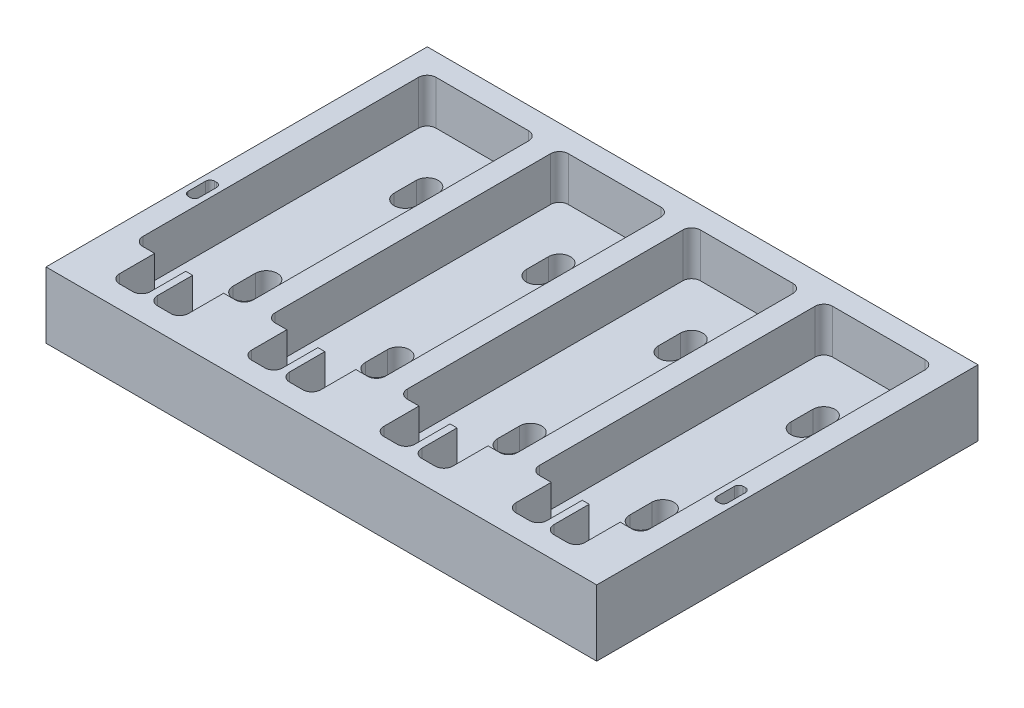
SolidWorks part; units mm, degrees
ref_plane "Front Plane" through (0, 0, 0) normal (0, 0, 1) x (1, 0, 0)
ref_plane "Top Plane" through (0, 0, 0) normal (0, 1, 0) x (1, 0, 0)
ref_plane "Right Plane" through (0, 0, 0) normal (1, 0, 0) x (0, 0, -1)
sketch "Sketch3" plane through (0, 0, 0) normal (0, 1, 0) x (1, 0, 0)
  line L0 (85.09, 19.05) -> (111.76, 19.05)
  line L1 (0, 0) -> (158.75, 0)
  line L2 (0, 0) -> (0, 109.9058)
  line L3 (0, 109.9058) -> (158.75, 109.9058)
  line L4 (158.75, 0) -> (158.75, 109.9058)
  line L6 (6.35, 95.9358) -> (6.35, 24.765)
  line L7 (21.4376, 19.05) -> (23.0124, 19.05)
  line L8 (38.1, 101.0158) -> (38.1, 29.845)
  line L9 (44.45, 101.0158) -> (44.45, 29.845)
  line L10 (59.5884, 19.05) -> (61.0616, 19.05)
  line L11 (76.2, 101.0158) -> (76.2, 29.845)
  line L13 (82.55, 101.0158) -> (82.55, 29.8069)
  line L14 (90.0544, 19.05) -> (106.7956, 19.05)
  line L15 (114.3, 101.0158) -> (114.3, 29.4066)
  line L18 (123.19, 19.05) -> (149.86, 19.05)
  line L20 (22.225, 103.5558) -> (22.225, 19.05) construction
  line L21 (21.4376, 19.05) -> (36.8492, 19.05) construction
  line L22 (88.4842, 19.05) -> (88.4842, 8.89)
  line L23 (94.885, 6.35) -> (91.0242, 6.35)
  line L24 (97.425, 19.05) -> (97.425, 8.89)
  line L25 (60.325, 19.05) -> (60.325, 0) construction
  line L26 (98.425, 19.05) -> (98.425, 0) construction
  line L27 (136.525, 19.05) -> (136.525, 0) construction
  line L28 (50.3842, 19.05) -> (59.325, 19.05)
  line L29 (50.3842, 19.05) -> (50.3842, 8.89)
  line L30 (52.9242, 6.35) -> (56.785, 6.35)
  line L31 (59.325, 19.05) -> (59.325, 8.89)
  line L32 (68.8492, 19.05) -> (78.3492, 19.05)
  line L33 (22.225, 19.05) -> (22.225, 0) construction
  line L34 (23.225, 19.05) -> (23.225, 8.89)
  line L35 (29.6258, 6.35) -> (25.765, 6.35)
  line L36 (12.2842, 19.05) -> (21.225, 19.05)
  line L37 (12.2842, 19.05) -> (12.2842, 8.89)
  line L38 (14.8242, 6.35) -> (18.685, 6.35)
  line L39 (21.225, 19.05) -> (21.225, 8.89)
  line L40 (97.425, 19.05) -> (88.4842, 19.05)
  line L41 (70.2658, 19.05) -> (70.2658, 8.89)
  line L42 (67.7258, 6.35) -> (63.865, 6.35)
  line L43 (61.325, 19.05) -> (61.325, 8.89)
  line L44 (108.3492, 19.05) -> (98.8492, 19.05)
  line L45 (138.3492, 19.05) -> (128.8492, 19.05) construction
  line L46 (108.3658, 19.05) -> (108.3658, 8.89)
  line L47 (101.965, 6.35) -> (105.8258, 6.35)
  line L48 (99.425, 19.05) -> (99.425, 8.89)
  line L49 (138.3492, 19.05) -> (128.8492, 19.05)
  line L50 (126.5842, 19.05) -> (126.5842, 8.89)
  line L51 (132.985, 6.35) -> (129.1242, 6.35)
  line L52 (32.1658, 19.05) -> (32.1658, 8.89)
  line L53 (135.525, 19.05) -> (135.525, 8.89)
  line L54 (135.525, 19.05) -> (126.5842, 19.05)
  line L55 (60.325, 19.05) -> (60.325, 103.5558) construction
  line L57 (98.425, 103.5558) -> (98.425, 19.05) construction
  line L58 (136.525, 100.33) -> (136.525, 19.05) construction
  line L59 (146.4658, 19.05) -> (146.4658, 8.89)
  line L60 (140.065, 6.35) -> (143.9258, 6.35)
  line L61 (137.525, 19.05) -> (137.525, 8.89)
  line L63 (8.89, 103.5558) -> (35.56, 103.5558)
  line L64 (6.35, 101.0158) -> (6.35, 21.59)
  line L65 (8.89, 19.05) -> (35.56, 19.05)
  line L66 (38.1, 101.0158) -> (38.1, 21.59)
  line L67 (46.99, 103.5558) -> (73.66, 103.5558)
  line L68 (44.45, 101.0158) -> (44.45, 21.59)
  line L69 (46.99, 19.05) -> (73.66, 19.05)
  line L70 (76.2, 101.0158) -> (76.2, 21.59)
  line L71 (85.09, 103.5558) -> (111.76, 103.5558)
  line L72 (82.55, 101.0158) -> (82.55, 21.59)
  line L74 (123.19, 103.5558) -> (149.86, 103.5558)
  line L76 (114.3, 101.0158) -> (114.3, 21.59)
  line L77 (120.65, 101.0158) -> (120.65, 21.59)
  line L78 (123.19, 19.05) -> (149.86, 19.05)
  line L79 (152.4, 101.0158) -> (152.4, 21.59)
  arc A0 (152.4, 101.0158) -> (149.86, 103.5558) centre (149.86, 101.0158) ccw
  arc A1 (123.19, 19.05) -> (120.65, 21.59) centre (123.19, 21.59) cw
  arc A2 (85.09, 103.5558) -> (82.55, 101.0158) centre (85.09, 101.0158) ccw
  arc A3 (114.3, 101.0158) -> (111.76, 103.5558) centre (111.76, 101.0158) ccw
  arc A4 (123.19, 103.5558) -> (120.65, 101.0158) centre (123.19, 101.0158) ccw
  arc A5 (152.4, 21.59) -> (149.86, 19.05) centre (149.86, 21.59) cw
  arc A6 (38.1, 101.0158) -> (35.56, 103.5558) centre (35.56, 101.0158) ccw
  arc A7 (8.89, 103.5558) -> (6.35, 101.0158) centre (8.89, 101.0158) ccw
  arc A8 (8.89, 19.05) -> (6.35, 21.59) centre (8.89, 21.59) cw
  arc A9 (38.1, 21.59) -> (35.56, 19.05) centre (35.56, 21.59) cw
  arc A10 (44.45, 21.59) -> (46.99, 19.05) centre (46.99, 21.59) ccw
  arc A11 (73.66, 19.05) -> (76.2, 21.59) centre (73.66, 21.59) ccw
  arc A12 (46.99, 103.5558) -> (44.45, 101.0158) centre (46.99, 101.0158) ccw
  arc A13 (76.2, 101.0158) -> (73.66, 103.5558) centre (73.66, 101.0158) ccw
  arc A14 (114.3, 21.59) -> (111.76, 19.05) centre (111.76, 21.59) cw
  arc A15 (82.55, 21.59) -> (85.09, 19.05) centre (85.09, 21.59) ccw
  arc A16 (126.5842, 8.89) -> (129.1242, 6.35) centre (129.1242, 8.89) ccw
  arc A17 (132.985, 6.35) -> (135.525, 8.89) centre (132.985, 8.89) ccw
  arc A18 (140.065, 6.35) -> (137.525, 8.89) centre (140.065, 8.89) cw
  arc A19 (146.4658, 8.89) -> (143.9258, 6.35) centre (143.9258, 8.89) cw
  arc A20 (108.3658, 8.89) -> (105.8258, 6.35) centre (105.8258, 8.89) cw
  arc A21 (101.965, 6.35) -> (99.425, 8.89) centre (101.965, 8.89) cw
  arc A22 (94.885, 6.35) -> (97.425, 8.89) centre (94.885, 8.89) ccw
  arc A23 (88.4842, 8.89) -> (91.0242, 6.35) centre (91.0242, 8.89) ccw
  arc A24 (70.2658, 8.89) -> (67.7258, 6.35) centre (67.7258, 8.89) cw
  arc A25 (63.865, 6.35) -> (61.325, 8.89) centre (63.865, 8.89) cw
  arc A26 (56.785, 6.35) -> (59.325, 8.89) centre (56.785, 8.89) ccw
  arc A27 (50.3842, 8.89) -> (52.9242, 6.35) centre (52.9242, 8.89) ccw
  arc A28 (29.6258, 6.35) -> (32.1658, 8.89) centre (29.6258, 8.89) ccw
  arc A29 (23.225, 8.89) -> (25.765, 6.35) centre (25.765, 8.89) ccw
  arc A30 (18.685, 6.35) -> (21.225, 8.89) centre (18.685, 8.89) ccw
  arc A31 (12.2842, 8.89) -> (14.8242, 6.35) centre (14.8242, 8.89) ccw
  point P79 (82.55, 103.5558)
  point P82 (114.3, 103.5558)
  point P89 (38.1, 103.5558)
  point P92 (6.35, 103.5558)
  point P95 (6.35, 19.05)
  point P98 (38.1, 19.05)
  point P101 (44.45, 19.05)
  point P112 (76.2, 19.05)
  point P115 (44.45, 103.5558)
  point P119 (22.225, 103.5558)
  point P120 (60.325, 103.5558)
  point P130 (98.425, 103.5558)
  point P131 (136.525, 103.5558)
  point P133 (76.2, 103.5558)
  point P138 (82.55, 19.05)
  point P141 (126.5842, 6.35)
  point P144 (135.525, 6.35)
  point P147 (137.525, 6.35)
  point P150 (146.4658, 6.35)
  point P153 (108.3658, 6.35)
  point P156 (99.425, 6.35)
  point P159 (97.425, 6.35)
  point P162 (88.4842, 6.35)
  point P165 (70.2658, 6.35)
  point P168 (61.325, 6.35)
  point P171 (59.325, 6.35)
  point P174 (50.3842, 6.35)
  point P177 (32.1658, 6.35)
  point P180 (23.225, 6.35)
  point P183 (21.225, 6.35)
  point P186 (12.2842, 6.35)
  dimension "D22" = 2.54
  dimension "D25" = 103.5558
  dimension "D26" = 31.75
  dimension "D27" = 2.54
  dimension "D28" = 6.35
  dimension "D5" = 2.54
  dimension "D17" = 2.54
  dimension "D24" = 2.54
  dimension "D1" = 6.35
  dimension "D3" = 6.35
  dimension "D4" = 103.5558
  dimension "D6" = 6.35
  dimension "D7" = 1
  dimension "D8" = 8.9408
  dimension "D9" = 8.9408
  dimension "D10" = 8.9408
  dimension "D11" = 31.75
  dimension "D12" = 6.35
  dimension "D13" = 6.35
  dimension "D14" = 6.35
  dimension "D15" = 31.75
  dimension "D16" = 31.75
  dimension "D18" = 8.9408
  dimension "D19" = 1
  dimension "D20" = 1
  dimension "D21" = 1
  dimension "D23" = 12.7
extrude "Boss-Extrude4" add sketch "Sketch3" against normal blind 19.05 contours L39 L7 L37 L38 | L7 | L8 L6 L7 | L31 L10 L29 L30 | L11 L9 L10 | L15 L13 L14 | L24 L14 L22 L23 | L14 | L53 L18 L50 L51 | L18 | L10 | L1 L4 L3 L2 L10 L31 L30 L29 L9 L11 L7 L39 L38 L37 L6 L8 L14 L24 L23 L22 L13 L15 L18 L53 L51 L50 | L18 | L52 L7 L34 L35 | A25 L42 A24 L41 L32 L69 L43 | A21 L47 A20 L46 L0 L44 L48 | A19 L59 L18 L61 A18 L60 region at (98.425, 0, -61.3029) region at (92.9546, 0, -12.8445) region at (103.8954, 0, -12.8445) region at (79.375, 0, -49.7076) region at (22.225, 0, -61.3029) region at (16.7546, 0, -12.8445) region at (27.6954, 0, -12.8445) region at (60.325, 0, -61.3029) region at (54.8546, 0, -12.8445) region at (65.7954, 0, -12.8445) region at (136.525, 0, -61.3029) region at (131.0546, 0, -12.8445) region at (141.9954, 0, -12.8445)
extrude "Cut-Extrude7" cut sketch "Sketch3<12>" against normal blind 12.7 contours L8 L6 L7 | L11 L9 L10 L32 | L31 L10 L29 L30 | L32 L43 L42 L41 L10 | L15 L13 L14 L40 L44 | L24 L40 L14 L22 L23 | L18 L49 | L53 L18 L50 L51 | L18 L61 L60 L59 | L44 L48 L47 L46 L14 | L39 L7 L37 L38 | L52 L7 L34 L35 | L37 A31 L38 A30 L39 L36 region at (98.425, 0, -61.3029) region at (92.9546, 0, -12.8445) region at (103.8954, 0, -12.8445) region at (22.225, 0, -61.3029) region at (16.7546, 0, -12.8445) region at (27.6954, 0, -12.8445) region at (60.325, 0, -61.3029) region at (54.8546, 0, -12.8445) region at (65.7954, 0, -12.8445) region at (136.525, 0, -61.3029) region at (131.0546, 0, -12.8445) region at (141.9954, 0, -12.8445)
sketch "Sketch3<12>" plane through (0, 0, 0) normal (0, 1, 0) x (1, 0, 0) same geometry as "Sketch3"
sketch "Sketch5" plane through (0, -12.7, 0) normal (0, 1, 0) x (1, 0, 0)
  line L0 (22.225, 103.5558) -> (22.225, 0) construction
  line L2 (0, 0) -> (158.75, 0) construction
  line L3 (60.325, 103.5558) -> (60.325, 0) construction
  line L5 (98.425, 103.5558) -> (98.425, 0) construction
  line L7 (136.525, 103.5558) -> (136.525, 0) construction
  line L9 (22.225, 87.6808) -> (22.225, 81.3308) construction
  line L10 (25.4, 87.6808) -> (25.4, 81.3308)
  line L11 (19.05, 87.6808) -> (19.05, 81.3308)
  line L12 (22.225, 41.275) -> (22.225, 34.925) construction
  line L13 (25.4, 41.275) -> (25.4, 34.925)
  line L14 (19.05, 41.275) -> (19.05, 34.925)
  line L15 (60.325, 34.925) -> (60.325, 41.275) construction
  line L16 (57.15, 34.925) -> (57.15, 41.275)
  line L17 (63.5, 34.925) -> (63.5, 41.275)
  line L18 (60.325, 81.3308) -> (60.325, 87.6808) construction
  line L19 (57.15, 81.3308) -> (57.15, 87.6808)
  line L20 (63.5, 81.3308) -> (63.5, 87.6808)
  line L21 (98.425, 87.6808) -> (98.425, 81.3308) construction
  line L22 (101.6, 87.6808) -> (101.6, 81.3308)
  line L23 (95.25, 87.6808) -> (95.25, 81.3308)
  line L24 (98.425, 41.275) -> (98.425, 34.925) construction
  line L25 (101.6, 41.275) -> (101.6, 34.925)
  line L26 (95.25, 41.275) -> (95.25, 34.925)
  line L27 (136.525, 41.275) -> (136.525, 34.925) construction
  line L28 (139.7, 41.275) -> (139.7, 34.925)
  line L29 (133.35, 41.275) -> (133.35, 34.925)
  line L30 (136.525, 87.6808) -> (136.525, 81.3308) construction
  line L31 (139.7, 87.6808) -> (139.7, 81.3308)
  line L32 (133.35, 87.6808) -> (133.35, 81.3308)
  line L33 (21.225, 19.05) -> (23.225, 19.05) construction
  line L35 (59.325, 19.05) -> (61.325, 19.05) construction
  line L36 (97.425, 19.05) -> (99.425, 19.05) construction
  line L37 (135.525, 19.05) -> (137.525, 19.05) construction
  line L40 (8.89, 103.5558) -> (35.56, 103.5558) construction
  line L41 (46.99, 103.5558) -> (73.66, 103.5558) construction
  line L42 (85.09, 103.5558) -> (111.76, 103.5558) construction
  line L43 (123.19, 103.5558) -> (149.86, 103.5558) construction
  arc A0 (25.4, 87.6808) -> (19.05, 87.6808) centre (22.225, 87.6808) ccw
  arc A1 (19.05, 81.3308) -> (25.4, 81.3308) centre (22.225, 81.3308) ccw
  arc A2 (25.4, 41.275) -> (19.05, 41.275) centre (22.225, 41.275) ccw
  arc A3 (19.05, 34.925) -> (25.4, 34.925) centre (22.225, 34.925) ccw
  arc A4 (57.15, 34.925) -> (63.5, 34.925) centre (60.325, 34.925) ccw
  arc A5 (63.5, 41.275) -> (57.15, 41.275) centre (60.325, 41.275) ccw
  arc A6 (57.15, 81.3308) -> (63.5, 81.3308) centre (60.325, 81.3308) ccw
  arc A7 (63.5, 87.6808) -> (57.15, 87.6808) centre (60.325, 87.6808) ccw
  arc A8 (101.6, 87.6808) -> (95.25, 87.6808) centre (98.425, 87.6808) ccw
  arc A9 (95.25, 81.3308) -> (101.6, 81.3308) centre (98.425, 81.3308) ccw
  arc A10 (101.6, 41.275) -> (95.25, 41.275) centre (98.425, 41.275) ccw
  arc A11 (95.25, 34.925) -> (101.6, 34.925) centre (98.425, 34.925) ccw
  arc A12 (139.7, 41.275) -> (133.35, 41.275) centre (136.525, 41.275) ccw
  arc A13 (133.35, 34.925) -> (139.7, 34.925) centre (136.525, 34.925) ccw
  arc A14 (139.7, 87.6808) -> (133.35, 87.6808) centre (136.525, 87.6808) ccw
  arc A15 (133.35, 81.3308) -> (139.7, 81.3308) centre (136.525, 81.3308) ccw
  point P20 (22.225, 84.5058)
  point P25 (22.225, 38.1)
  point P32 (60.325, 38.1)
  point P39 (60.325, 84.5058)
  point P46 (98.425, 84.5058)
  point P53 (98.425, 38.1)
  point P60 (136.525, 38.1)
  point P67 (136.525, 84.5058)
  dimension "D1" = 6.35
  dimension "D2" = 6.35
  dimension "D3" = 6.35
  dimension "D4" = 6.35
  dimension "D5" = 6.35
  dimension "D6" = 6.35
  dimension "D7" = 19.05
  dimension "D8" = 19.05
  dimension "D9" = 19.05
  dimension "D10" = 6.35
  dimension "D11" = 6.35
  dimension "D12" = 19.05
  dimension "D13" = 6.35
  dimension "D14" = 6.35
  dimension "D15" = 19.05
  dimension "D16" = 6.35
  dimension "D17" = 6.35
  dimension "D18" = 19.05
  dimension "D19" = 6.35
  dimension "D20" = 6.35
  dimension "D21" = 19.05
  dimension "D22" = 6.35
  dimension "D23" = 6.35
  dimension "D24" = 19.05
extrude "Cut-Extrude8" cut sketch "Sketch5" against normal through all
sketch "Sketch7" plane through (0, 0, 0) normal (0, 1, 0) x (1, 0, 0)
  line L0 (0, 0) -> (0, 109.9058) construction
  line L1 (2.8575, 45.72) -> (3.4925, 45.72)
  line L2 (1.5875, 44.45) -> (1.5875, 39.37)
  line L3 (2.8575, 38.1) -> (3.4925, 38.1)
  line L4 (4.7625, 44.45) -> (4.7625, 39.37)
  line L5 (0, 0) -> (158.75, 0) construction
  line L6 (79.375, 109.9058) -> (79.375, 0) construction
  line L7 (0, 109.9058) -> (158.75, 109.9058) construction
  line L8 (153.9875, 44.45) -> (153.9875, 39.37)
  line L9 (155.8925, 38.1) -> (155.2575, 38.1)
  line L10 (157.1625, 44.45) -> (157.1625, 39.37)
  line L11 (155.8925, 45.72) -> (155.2575, 45.72)
  arc A0 (3.4925, 38.1) -> (4.7625, 39.37) centre (3.4925, 39.37) ccw
  arc A1 (1.5875, 39.37) -> (2.8575, 38.1) centre (2.8575, 39.37) ccw
  arc A2 (3.4925, 45.72) -> (4.7625, 44.45) centre (3.4925, 44.45) cw
  arc A3 (2.8575, 45.72) -> (1.5875, 44.45) centre (2.8575, 44.45) ccw
  arc A4 (153.9875, 39.37) -> (155.2575, 38.1) centre (155.2575, 39.37) ccw
  arc A5 (155.8925, 38.1) -> (157.1625, 39.37) centre (155.8925, 39.37) ccw
  arc A6 (157.1625, 44.45) -> (155.8925, 45.72) centre (155.8925, 44.45) ccw
  arc A7 (153.9875, 44.45) -> (155.2575, 45.72) centre (155.2575, 44.45) cw
  point P18 (4.7625, 38.1)
  point P21 (1.5875, 38.1)
  point P24 (4.7625, 45.72)
  point P27 (1.5875, 45.72)
  point P30 (153.9875, 38.1)
  point P33 (157.1625, 38.1)
  point P36 (157.1625, 45.72)
  point P39 (153.9875, 45.72)
  dimension "D5" = 1.27
  dimension "D6" = 1.27
  dimension "D1" = 3.175
  dimension "D2" = 1.5875
  dimension "D3" = 7.62
  dimension "D4" = 38.1
extrude "Cut-Extrude9" cut sketch "Sketch7" against normal blind 5.08
